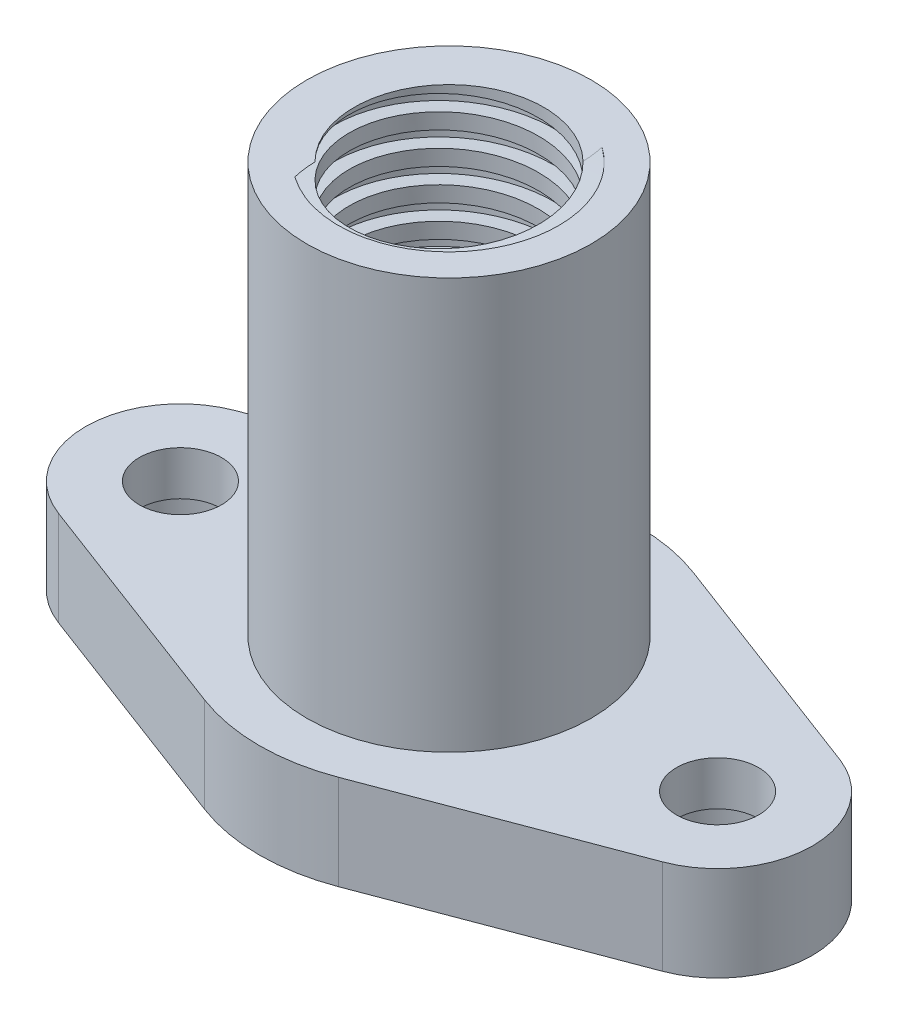
SolidWorks part; units mm, degrees
ref_plane "Front Plane" through (0, 0, 0) normal (0, 0, 1) x (1, 0, 0)
ref_plane "Top Plane" through (0, 0, 0) normal (0, 1, 0) x (1, 0, 0)
ref_plane "Right Plane" through (0, 0, 0) normal (1, 0, 0) x (0, 0, -1)
sketch "Sketch1" plane through (0, 0, 0) normal (0, 1, 0) x (1, 0, 0)
  line L0 (-10.5882, 28.0694) -> (-47.7941, 14.0347)
  line L1 (10.5882, 28.0694) -> (47.7941, 14.0347)
  line L3 (10.5882, -28.0694) -> (47.7941, -14.0347)
  line L4 (-10.5882, -28.0694) -> (-47.7941, -14.0347)
  arc A0 (-10.5882, -28.0694) -> (10.5882, -28.0694) centre (0, 0) ccw
  arc A2 (47.7941, -14.0347) -> (47.7941, 14.0347) centre (42.5, 0) ccw
  arc A3 (10.5882, 28.0694) -> (-10.5882, 28.0694) centre (0, 0) ccw
  arc A4 (-47.7941, 14.0347) -> (-47.7941, -14.0347) centre (-42.5, 0) ccw
  circle A5 centre (0, 0) radius 15
  dimension "D1" = 60
  dimension "D2" = 30
  dimension "D4" = 42.5
extrude "Boss-Extrude1" add sketch "Sketch1" along normal blind 15
sketch "Sketch2" plane through (0, 15, 0) normal (0, 1, 0) x (1, 0, 0)
  circle A2 centre (-42.5, 0) radius 6.5
  circle A5 centre (42.5, 0) radius 6.5
  dimension "D1" = 13
extrude "Cut-Extrude1" cut sketch "Sketch2" against normal blind 7
sketch "Sketch4" plane through (0, 8, 0) normal (0, 1, 0) x (1, 0, 0)
  circle A2 centre (-42.5, 0) radius 10
  circle A3 centre (42.5, 0) radius 10
  dimension "D1" = 20
  dimension "D2" = 20
extrude "Cut-Extrude2" cut sketch "Sketch4" against normal through all
sketch "Sketch5" plane through (0, 15, 0) normal (0, 1, 0) x (1, 0, 0)
  circle A0 centre (0, 0) radius 22.5
  circle A1 centre (0, 0) radius 15 construction
  circle A2 centre (0, 0) radius 15
  dimension "D1" = 45
extrude "Boss-Extrude2" add sketch "Sketch5" along normal blind 65
sketch "Sketch6" plane through (0, 80, 0) normal (0, 1, 0) x (1, 0, 0)
  circle A0 centre (0, 0) radius 15 construction
  circle A1 centre (0, 0) radius 15
curve "Helix/Spiral1" pitch 5 height 108.75 radius 15 centre (0, 80, 0) axis (0, -1, 0) start towards (0, 0, 1)
ref_plane "Plane1" through (-10.6066, 80, 10.6066) normal (-0.7061, -0.053, -0.7061) x (-0.7041, -0.0528, 0.7081)
sketch "Sketch7" plane through (-10.6066, 80, 10.6066) normal (-0.7061, -0.053, -0.7061) x (-0.7041, -0.0528, 0.7081)
  line L1 (0, -2.5) -> (2.5, -2.5)
  line L2 (0, -2.5) -> (0, 0)
  line L3 (0, 0) -> (2.5, 0)
  line L4 (2.5, -2.5) -> (2.5, 0)
  line L5 (0, -2.5) -> (2.5, 0) construction
  line L6 (0, 0) -> (2.5, -2.5) construction
  point P0 (1.25, -1.25)
  dimension "D1" = 2.5
  dimension "D2" = 2.5
sweep "Cut-Sweep1" cut profiles "Sketch7" path "Helix/Spiral1" align with end faces yes
